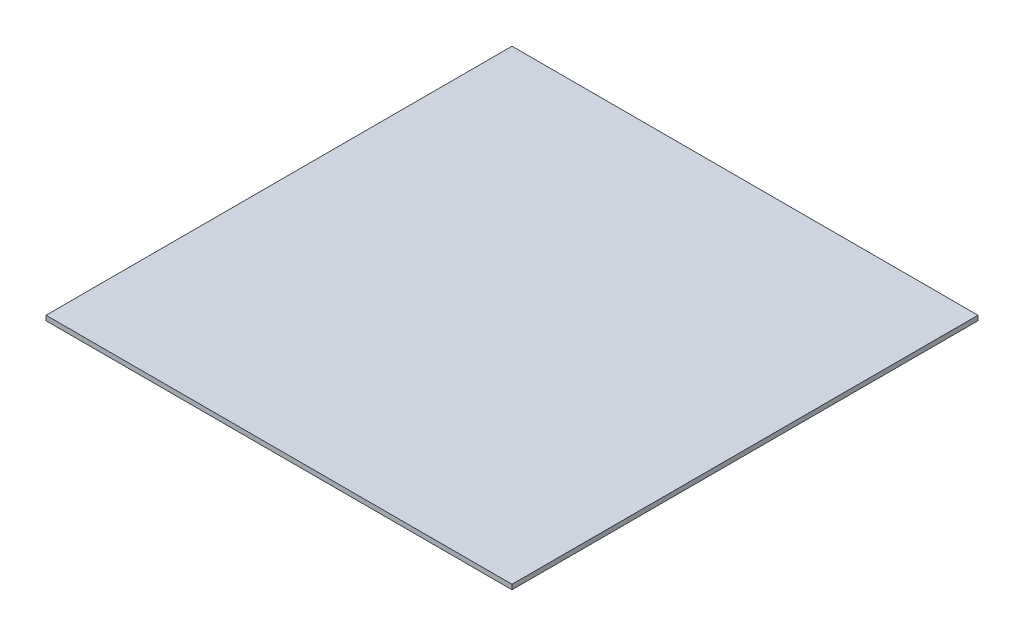
SolidWorks part; units mm, degrees
ref_plane "Front Plane" through (0, 0, 0) normal (0, 0, 1) x (1, 0, 0)
ref_plane "Top Plane" through (0, 0, 0) normal (0, 1, 0) x (1, 0, 0)
ref_plane "Right Plane" through (0, 0, 0) normal (1, 0, 0) x (0, 0, -1)
sketch "Sketch1" plane through (0, 0, 0) normal (0, 1, 0) x (1, 0, 0)
  line L0 (143.9399, -59.7611) -> (143.9399, 329.3962) construction
  line L1 (-50.6387, 329.3962) -> (338.5186, 329.3962)
  line L2 (-50.6387, 329.3962) -> (-50.6387, -59.7611)
  line L3 (-50.6387, -59.7611) -> (338.5186, -59.7611)
  line L4 (338.5186, 329.3962) -> (338.5186, -59.7611)
  line L5 (338.5186, 134.8175) -> (-50.6387, 134.8175) construction
  line L6 (-50.6387, 44.8175) -> (338.5186, 44.8175) construction
  line L7 (53.9399, 329.3962) -> (53.9399, -59.7611) construction
  line L8 (338.5186, 224.8175) -> (-50.6387, 224.8175) construction
  line L9 (233.9399, -59.7611) -> (233.9399, 329.3962) construction
  point P10 (143.9399, 44.8175)
  point P11 (233.9399, 134.8175)
  point P12 (53.9399, 134.8175)
  point P19 (143.9399, 134.8175)
  dimension "D1" = 90
  dimension "D2" = 4
extrude "Boss-Extrude1" add sketch "Sketch1" along normal blind 4
